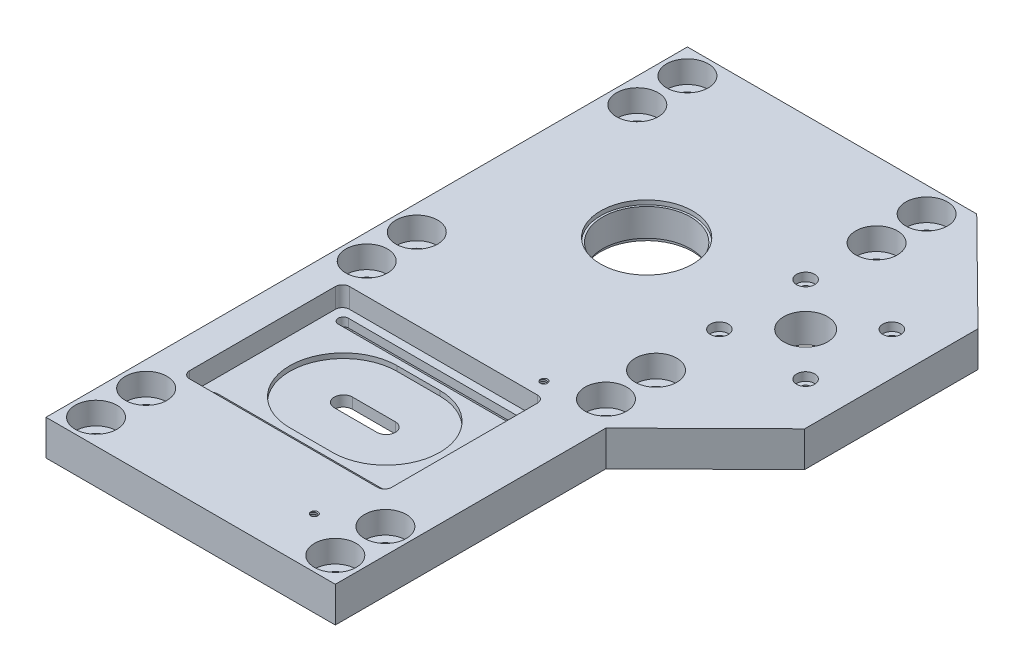
SolidWorks part; units mm, degrees
ref_plane "Front Plane" through (0, 0, 0) normal (0, 0, 1) x (1, 0, 0)
ref_plane "Top Plane" through (0, 0, 0) normal (0, 1, 0) x (1, 0, 0)
ref_plane "Right Plane" through (0, 0, 0) normal (1, 0, 0) x (0, 0, -1)
sketch "Sketch2" plane through (0, 0, 0) normal (0, 1, 0) x (1, 0, 0)
  line L0 (0, 163.9144) -> (104, 163.9144) construction
  line L1 (0, 0) -> (104, 0)
  line L2 (0, 0) -> (0, 230.564)
  line L3 (0, 230.564) -> (104, 230.564)
  line L4 (104, 0) -> (104, 97.2648)
  line L5 (52, 163.9144) -> (139.9602, 163.9144) construction
  line L6 (0, 97.2648) -> (104, 97.2648) construction
  line L7 (104, 230.564) -> (139.9602, 195.0626)
  line L14 (139.9602, 195.0626) -> (139.9602, 132.7662)
  line L15 (104, 97.2648) -> (139.9602, 132.7662)
  point P21 (52, 163.9144)
  point P22 (109.1754, 163.9144)
  dimension "D4" = 57.1754
  dimension "D1" = 104
  dimension "D2" = 230.564
  dimension "D3" = 66.6496
  dimension "D6" = 87.9602
extrude "Boss-Extrude1" add sketch "Sketch2" along normal blind 12.7
sketch "Sketch3" plane through (0, 12.7, 0) normal (0, 1, 0) x (1, 0, 0)
  line L0 (104, 230.564) -> (0, 230.564) construction
  line L1 (0, 230.564) -> (0, 0) construction
  line L3 (104, 230.564) -> (0, 230.564) construction
  line L4 (52, 230.564) -> (52, 0) construction
  line L5 (0, 0) -> (104, 0) construction
  circle A0 centre (52, 163.9144) radius 15.8242
  circle A1 centre (109.15, 163.9144) radius 7.874
  dimension "D2" = 31.6484
  dimension "D3" = 15.748
  dimension "D4" = 57.15
  dimension "D1" = 66.6496
extrude "Cut-Extrude1" cut sketch "Sketch3" against normal through all and the other way through all
hole_wizard "CBORE for M3 SHCS1" positions "Sketch4" profile "Sketch6" counterbore size "M3" standard "ANSI Metric"
sketch "Sketch4" plane through (0, 12.7, 0) normal (0, 1, 0) x (1, 0, 0)
  line L0 (52, 163.9144) -> (109.15, 163.9144) construction
  line L3 (93.65, 148.4144) -> (124.65, 148.4144) construction
  line L4 (93.65, 148.4144) -> (93.65, 179.4144) construction
  line L5 (93.65, 179.4144) -> (124.65, 179.4144) construction
  line L6 (124.65, 148.4144) -> (124.65, 179.4144) construction
  line L7 (93.65, 148.4144) -> (124.65, 179.4144) construction
  line L8 (93.65, 179.4144) -> (124.65, 148.4144) construction
  point P6 (124.65, 179.4144)
  point P27 (93.65, 148.4144)
  point P28 (93.65, 179.4144)
  point P29 (124.65, 148.4144)
  dimension "D1" = 57.15
  dimension "D2" = 31
  dimension "D3" = 31
sketch "Sketch6" plane through (124.65, 12.7, -148.4144) normal (1, 0, 0) x (0, 0, 1)
  line L0 (0, 0) -> (0, 15.1854)
  line L1 (0, 15.1854) -> (1.6, 14.224)
  line L2 (1.6, 14.224) -> (1.6, 3)
  line L3 (1.6, 3) -> (3.25, 3)
  line L4 (3.25, 3) -> (3.25, 0)
  line L5 (3.25, 0) -> (0, 0)
  line L10 (0, 15.1854) -> (-1.6, 14.224) construction
  line L11 (0, -6.35) -> (0, 107.95) construction
  dimension "Hole Dia." = 3.2
  dimension "Hole Depth" = 14.224
  dimension "C'Bore Dia." = 6.5
  dimension "C'Bore Depth" = 3
  dimension "Drill Angle" = 118
sketch "Sketch7" plane through (0, 0, 0) normal (0, -1, 0) x (1, 0, 0)
  circle A0 centre (109.15, -163.9144) radius 11.25
  dimension "D1" = 22.5
extrude "Cut-Extrude2" cut sketch "Sketch7" against normal blind 2.286
sketch "Sketch8" plane through (0, 12.7, 0) normal (0, 1, 0) x (1, 0, 0)
  circle A0 centre (52, 163.9144) radius 16.5608
  dimension "D1" = 33.1216
extrude "Cut-Extrude3" cut sketch "Sketch8" against normal blind 1.524
sketch "Sketch11" plane through (0, 0, 0) normal (0, -1, 0) x (1, 0, 0)
  circle A0 centre (52, -163.9144) radius 16.5608
  dimension "D1" = 33.1216
extrude "Cut-Extrude4" cut sketch "Sketch11" against normal blind 1.27
sketch "Sketch12" plane through (0, 12.7, 0) normal (0, 1, 0) x (1, 0, 0)
  line L0 (0, 66.9626) -> (104, 66.9626) construction
  line L1 (0, 230.564) -> (0, 0) construction
  line L2 (104, 0) -> (104, 97.2648) construction
  line L3 (47.625, 230.564) -> (47.625, 0) construction
  line L4 (104, 230.564) -> (0, 230.564) construction
  line L5 (0, 0) -> (104, 0) construction
  line L6 (39.9415, 66.9626) -> (55.3085, 66.9626) construction
  line L7 (39.9415, 70.2646) -> (55.3085, 70.2646)
  line L8 (39.9415, 63.6606) -> (55.3085, 63.6606)
  line L9 (0, 90.4626) -> (104, 90.4626) construction
  line L10 (0, 43.4626) -> (104, 43.4626) construction
  line L11 (16.4084, 90.4626) -> (78.8416, 90.4626) construction
  line L12 (16.4084, 43.4626) -> (78.8416, 43.4626) construction
  line L13 (16.4084, 90.4626) -> (78.8416, 90.4626) construction
  line L14 (16.4084, 92.2914) -> (78.8416, 92.2914)
  line L15 (16.4084, 88.6338) -> (78.8416, 88.6338)
  line L16 (16.4084, 43.4626) -> (78.8416, 43.4626) construction
  line L17 (16.4084, 41.6338) -> (78.8416, 41.6338)
  line L18 (16.4084, 45.2914) -> (78.8416, 45.2914)
  circle A0 centre (52, 163.9144) radius 16.5608 construction
  arc A1 (39.9415, 70.2646) -> (39.9415, 63.6606) centre (39.9415, 66.9626) ccw
  arc A2 (55.3085, 63.6606) -> (55.3085, 70.2646) centre (55.3085, 66.9626) ccw
  arc A3 (16.4084, 92.2914) -> (16.4084, 88.6338) centre (16.4084, 90.4626) ccw
  arc A4 (78.8416, 88.6338) -> (78.8416, 92.2914) centre (78.8416, 90.4626) ccw
  arc A5 (16.4084, 41.6338) -> (16.4084, 45.2914) centre (16.4084, 43.4626) cw
  arc A6 (78.8416, 45.2914) -> (78.8416, 41.6338) centre (78.8416, 43.4626) cw
  point P16 (47.625, 66.9626)
  point P28 (47.625, 90.4626)
  point P31 (47.625, 43.4626)
  point P32 (47.625, 90.4626)
  dimension "D1" = 96.9518
  dimension "D4" = 3.302
  dimension "D8" = 1.8288
  dimension "D2" = 47.625
  dimension "D3" = 15.367
  dimension "D5" = 23.5
  dimension "D7" = 62.4332
extrude "Cut-Extrude5" cut sketch "Sketch12" against normal through all
sketch "Sketch14" plane through (0, 0, 0) normal (0, -1, 0) x (1, 0, 0)
  line L0 (58.6105, -66.9626) -> (36.6395, -66.9626) construction
  line L1 (78.8416, -90.4626) -> (16.4084, -90.4626) construction
  line L2 (78.8416, -93.7646) -> (16.4084, -93.7646)
  line L3 (78.8416, -87.1606) -> (16.4084, -87.1606)
  line L4 (78.8416, -43.4626) -> (16.4084, -43.4626) construction
  line L5 (78.8416, -40.1606) -> (16.4084, -40.1606)
  line L6 (78.8416, -46.7646) -> (16.4084, -46.7646)
  arc A1 (78.8416, -93.7646) -> (78.8416, -87.1606) centre (78.8416, -90.4626) ccw
  arc A4 (16.4084, -87.1606) -> (16.4084, -93.7646) centre (16.4084, -90.4626) ccw
  arc A5 (55.3085, -70.2646) -> (55.3085, -63.6606) centre (55.3085, -66.9626) ccw construction
  arc A6 (39.9415, -63.6606) -> (39.9415, -70.2646) centre (39.9415, -66.9626) ccw construction
  arc A7 (78.8416, -40.1606) -> (78.8416, -46.7646) centre (78.8416, -43.4626) cw
  arc A8 (16.4084, -46.7646) -> (16.4084, -40.1606) centre (16.4084, -43.4626) cw
  point P8 (47.625, -90.4626)
  point P18 (47.625, -43.4626)
  dimension "D1" = 3.302
extrude "Cut-Extrude7" cut sketch "Sketch14" against normal blind 2.54
sketch "Sketch15" plane through (0, 12.7, 0) normal (0, 1, 0) x (1, 0, 0)
  line L0 (78.8416, 92.2914) -> (16.4084, 92.2914) construction
  line L2 (11.303, 95.2582) -> (83.947, 95.2582)
  line L3 (11.303, 95.2582) -> (11.303, 37.7526)
  line L4 (11.303, 37.7526) -> (83.947, 37.7526)
  line L5 (83.947, 95.2582) -> (83.947, 37.7526)
  dimension "D1" = 72.644
  dimension "D2" = 57.5056
  dimension "D3" = 5.1054
  dimension "D4" = 2.9668
extrude "Cut-Extrude8" cut sketch "Sketch15" against normal blind 7.112
sketch "Sketch16" plane through (0, 5.588, 0) normal (0, 1, 0) x (1, 0, 0)
  line L0 (39.9415, 70.2646) -> (55.3085, 63.6606) construction
  line L1 (39.9415, 66.9626) -> (55.3085, 66.9626) construction
  line L2 (39.9415, 86.2666) -> (55.3085, 86.2666)
  line L3 (39.9415, 47.6586) -> (55.3085, 47.6586)
  arc A0 (39.9415, 86.2666) -> (39.9415, 47.6586) centre (39.9415, 66.9626) ccw
  arc A1 (55.3085, 47.6586) -> (55.3085, 86.2666) centre (55.3085, 66.9626) ccw
  point P6 (47.625, 66.9626)
  dimension "D1" = 19.304
extrude "Cut-Extrude9" cut sketch "Sketch16" against normal blind 1.778
fillet "Fillet1" radius 2.54 4 edges at (83.947, 9.144, -37.7526) (11.303, 9.144, -37.7526) (83.947, 9.144, -95.2582) (11.303, 9.144, -95.2582)
hole_wizard "CBORE for M8 SHCS1" positions "Sketch18" profile "Sketch20" counterbore size "M8" standard "ANSI Metric" end condition through all
sketch "Sketch18" plane through (0, 12.7, 0) normal (0, 1, 0) x (1, 0, 0)
  point P0 (9, 9)
  point P3 (9, 27)
  point P6 (9, 106.282)
  point P9 (9, 124.282)
  point P12 (9, 203.564)
  point P15 (9, 221.564)
  point P18 (95, 221.564)
  point P21 (95, 203.564)
  point P24 (95, 124.282)
  point P27 (95, 106.282)
  point P30 (95, 27)
  point P33 (95, 9)
sketch "Sketch20" plane through (9, 12.7, -9) normal (1, 0, 0) x (0, 0, 1)
  line L0 (0, 0) -> (0, 12.7)
  line L1 (0, 12.7) -> (4.2, 12.7)
  line L3 (4.2, 12.7) -> (4.2, 8)
  line L4 (4.2, 8) -> (7.5, 8)
  line L5 (7.5, 8) -> (7.5, 0)
  line L7 (7.5, 0) -> (0, 0)
  line L11 (0, -6.35) -> (0, 107.95) construction
  dimension "Thru Hole Dia." = 8.4
  dimension "Thru Hole Depth" = 12.7
  dimension "C'Bore Dia." = 15
  dimension "C'Bore Depth" = 8
hole_wizard "Tap Drill for #4-40 Tap1" positions "Sketch21" profile "Sketch22" hole size "#4-40" standard "ANSI Inch"
sketch "Sketch21" plane through (0, 12.7, 0) normal (0, 1, 0) x (1, 0, 0)
  point P0 (78.2562, 18.0086)
  point P3 (78.2562, 100.5586)
sketch "Sketch22" plane through (78.2562, 12.7, -18.0086) normal (1, 0, 0) x (0, 0, 1)
  line L0 (0, 0) -> (0, 8.2992)
  line L1 (0, 8.2992) -> (1.1303, 7.62)
  line L2 (1.1303, 7.62) -> (1.1303, 0)
  line L5 (1.1303, 0) -> (0, 0)
  line L10 (0, 8.2992) -> (-1.1303, 7.62) construction
  line L11 (0, -6.35) -> (0, 107.95) construction
  dimension "Hole Dia." = 2.2606
  dimension "Hole Depth" = 7.62
  dimension "Drill Angle" = 118
thread "Thread1" pitch 0.635 method cut profile "Thread Profile1" start angle 0, offset 0.254, length 0, pitch 0.635, diameter 2.2606
ref_plane "Plane1" through (79.3865, 5.334, -100.5586) normal (0, 0, 1) x (1, 0, 0)
sketch "Thread Profile1" plane through (79.3865, 5.334, -100.5586) normal (0, 0, 1) x (1, 0, 0)
  line L0 (0, 0) -> (0, 0.635) construction
  line L1 (0, 0) -> (0.3437, 0.1984)
  line L2 (0.3437, 0.1984) -> (0.3437, 0.2778)
  line L3 (0.3437, 0.2778) -> (0, 0.4762)
  line L4 (0.3437, 0.2381) -> (0, 0.2381) construction
  line L11 (0, 0) -> (0, 0.4762)
  point P2 (0, 0)
  dimension "Pitch" = 0.635
  dimension "Profile_Angle" = 60
  dimension "Profile_Land" = 0.0794
  dimension "Profile_Height" = 0.3437
thread "Thread2" pitch 0.635 method cut profile "Thread Profile2" start angle 0, offset 0.254, length 0, pitch 0.635, diameter 2.2606
ref_plane "Plane2" through (79.3865, 5.334, -18.0086) normal (0, 0, 1) x (1, 0, 0)
sketch "Thread Profile2" plane through (79.3865, 5.334, -18.0086) normal (0, 0, 1) x (1, 0, 0)
  line L0 (0, 0) -> (0, 0.635) construction
  line L1 (0, 0) -> (0.3437, 0.1984)
  line L2 (0.3437, 0.1984) -> (0.3437, 0.2778)
  line L3 (0.3437, 0.2778) -> (0, 0.4762)
  line L4 (0.3437, 0.2381) -> (0, 0.2381) construction
  line L11 (0, 0) -> (0, 0.4762)
  point P2 (0, 0)
  dimension "Pitch" = 0.635
  dimension "Profile_Angle" = 60
  dimension "Profile_Land" = 0.0794
  dimension "Profile_Height" = 0.3437
